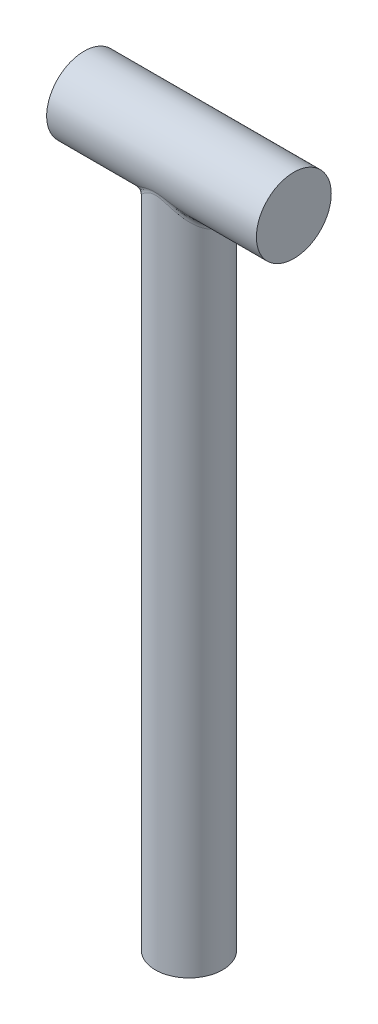
SolidWorks part; units mm, degrees
ref_plane "Alzado" through (0, 0, 0) normal (0, 0, 1) x (1, 0, 0)
ref_plane "Planta" through (0, 0, 0) normal (0, 1, 0) x (1, 0, 0)
ref_plane "Vista lateral" through (0, 0, 0) normal (1, 0, 0) x (0, 0, -1)
sketch "Croquis1" plane through (0, 0, 0) normal (0, 0, 1) x (1, 0, 0)
  line L0 (0, 0) -> (0, 46) construction
  line L1 (0, 46) -> (2.25, 46)
  line L2 (2.25, 46) -> (2.25, 0)
  line L3 (2.25, 0) -> (0, 0)
  line L4 (0, 0) -> (0, 46)
  dimension "D1" = 46
  dimension "D2" = 4.5
revolve "Revolución1" add sketch "Croquis1" angle 360 about L0
sketch "Croquis2" plane through (0, 0, 0) normal (1, 0, 0) x (0, 0, -1)
  line L0 (-2.25, 0) -> (2.25, 0) construction
  line L1 (0, 45.6463) -> (0, 33.7208) construction
  line L2 (-2.25, 46) -> (2.25, 46) construction
  circle A0 centre (0, 46) radius 2.5
  point P14 (0, 46)
  dimension "D1" = 5
  dimension "D2" = 46
extrude "Saliente-Extruir1" add sketch "Croquis2" along normal blind 7 and the other way blind 7
fillet "Redondeo3" radius 0.5 1 edges at (0.1901, 44.8938, 2.242)
ref_plane "Plane1" through (0, 46, 0) normal (0, 1, 0) x (1, 0, 0)
